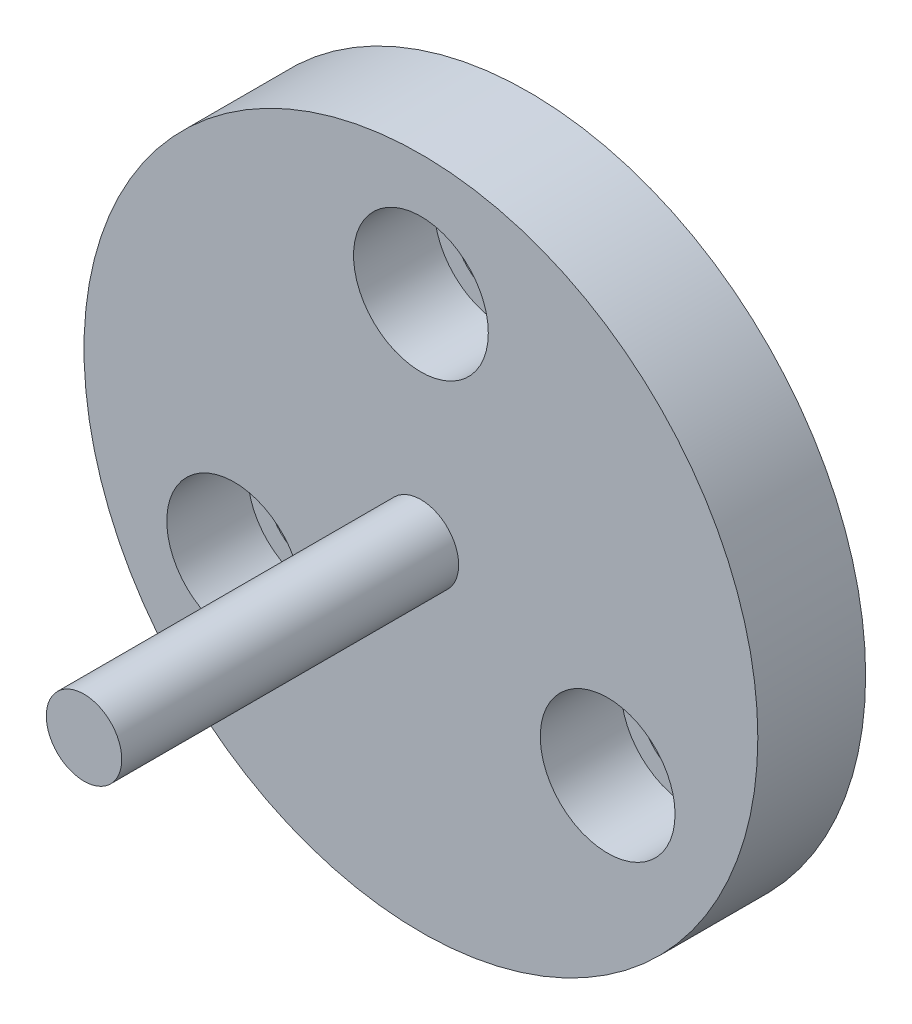
SolidWorks part; units mm, degrees
note: The reader was unsure of these and kept them because the rebuilt part matched: shared geometry of "草图1<3>", "草图3<3>".
ref_plane "前视基准面" through (0, 0, 0) normal (0, 0, 1) x (1, 0, 0)
ref_plane "上视基准面" through (0, 0, 0) normal (0, 1, 0) x (1, 0, 0)
ref_plane "右视基准面" through (0, 0, 0) normal (1, 0, 0) x (0, 0, -1)
other "Configuration Table"
sketch "草图1" plane through (0, 0, 0) normal (0, 0, 1) x (1, 0, 0)
  line L0 (0, 0) -> (1.6914, 0.6156) construction
  line L1 (0, 0) -> (1.5832, 0.5954)
  line L2 (0, 0) -> (1.5832, -0.5954)
  line L3 (0, 0) -> (1.6914, -0.6156) construction
  line L4 (0, 0) -> (2.55, 0) construction
  line L5 (1.6914, 0.6156) -> (1.6914, -0.6156) construction
  circle A0 centre (0, 0) radius 1.65
  circle A1 centre (0, 0) radius 2.55
  circle A2 centre (0, 0) radius 1.6914 construction
  circle A3 centre (0, 0) radius 1.8 construction
  circle A4 centre (0, 0) radius 3
  spline S0 degree 4 poles (1.5832, 0.5954) (1.5953, 0.5999) (1.6299, 0.61) (1.6985, 0.6188) (1.8107, 0.6176) (1.9542, 0.5935) (2.1323, 0.5368) (2.3288, 0.4397) (2.527, 0.3033) (2.7182, 0.1281) (2.8863, -0.0692) (3.0309, -0.2841) (3.1583, -0.5243) (3.284, -0.8365) (3.3855, -1.2255) (3.4358, -1.6902) (3.4119, -2.2085) (3.3126, -2.7182) (3.1474, -3.2089) (2.918, -3.6756) (2.6387, -4.1089) (2.3029, -4.5102) (1.9385, -4.866) (1.5141, -5.1906) (1.1742, -5.4065) (0.7714, -5.6132) (0.5343, -5.7151) (0.2601, -5.8236) (0.1183, -5.8645) (-0.005, -5.9055) (-0.0434, -5.9147) (-0.0704, -5.9226) (-0.0848, -5.927) knots 0 0 0 0 0 0.005604 0.015718 0.02996 0.048734 0.068727 0.096889 0.125051 0.153212 0.181374 0.209535 0.237696 0.271429 0.327752 0.384075 0.440398 0.496721 0.553044 0.609367 0.66569 0.722013 0.778336 0.834659 0.890982 0.909091 0.954545 0.977273 0.988636 0.994318 1 1 1 1 1 construction
  spline S1 degree 4 poles (1.5832, 0.5954) (1.5953, 0.5999) (1.6299, 0.61) (1.6985, 0.6188) (1.8107, 0.6176) (1.9542, 0.5935) (2.1323, 0.5368) (2.3288, 0.4397) (2.527, 0.3033) (2.7182, 0.1281) (2.8863, -0.0692) (3.0309, -0.2841) (3.1583, -0.5243) (3.284, -0.8365) (3.3855, -1.2255) (3.4358, -1.6902) (3.4119, -2.2085) (3.3126, -2.7182) (3.1474, -3.2089) (2.918, -3.6756) (2.6387, -4.1089) (2.3029, -4.5102) (1.9385, -4.866) (1.5141, -5.1906) (1.1742, -5.4065) (0.8753, -5.5599) (0.734, -5.626) (0.6996, -5.6416) knots 0 0 0 0 0 0.005604 0.015718 0.02996 0.048734 0.068727 0.096889 0.125051 0.153212 0.181374 0.209535 0.237696 0.271429 0.327752 0.384075 0.440398 0.496721 0.553044 0.609367 0.66569 0.722013 0.778336 0.834659 0.890982 0.909091 0.909091 0.909091 0.909091 0.909091
  spline S2 degree 4 poles (1.5832, -0.5954) (1.5953, -0.5999) (1.6299, -0.61) (1.6985, -0.6188) (1.8107, -0.6176) (1.9542, -0.5935) (2.1323, -0.5368) (2.3288, -0.4397) (2.527, -0.3033) (2.7182, -0.1281) (2.8863, 0.0692) (3.0309, 0.2841) (3.1583, 0.5243) (3.284, 0.8365) (3.3855, 1.2255) (3.4358, 1.6902) (3.4119, 2.2085) (3.3126, 2.7182) (3.1474, 3.2089) (2.918, 3.6756) (2.6387, 4.1089) (2.3029, 4.5102) (1.9385, 4.866) (1.5141, 5.1906) (1.1742, 5.4065) (0.7714, 5.6132) (0.5343, 5.7151) (0.2601, 5.8236) (0.1183, 5.8645) (-0.005, 5.9055) (-0.0434, 5.9147) (-0.0704, 5.9226) (-0.0848, 5.927) knots 0 0 0 0 0 0.005604 0.015718 0.02996 0.048734 0.068727 0.096889 0.125051 0.153212 0.181374 0.209535 0.237696 0.271429 0.327752 0.384075 0.440398 0.496721 0.553044 0.609367 0.66569 0.722013 0.778336 0.834659 0.890982 0.909091 0.954545 0.977273 0.988636 0.994318 1 1 1 1 1 construction
  spline S3 degree 4 poles (1.5832, -0.5954) (1.5953, -0.5999) (1.6299, -0.61) (1.6985, -0.6188) (1.8107, -0.6176) (1.9542, -0.5935) (2.1323, -0.5368) (2.3288, -0.4397) (2.527, -0.3033) (2.7182, -0.1281) (2.8863, 0.0692) (3.0309, 0.2841) (3.1583, 0.5243) (3.284, 0.8365) (3.3855, 1.2255) (3.4358, 1.6902) (3.4119, 2.2085) (3.3126, 2.7182) (3.1474, 3.2089) (2.918, 3.6756) (2.6387, 4.1089) (2.3029, 4.5102) (1.9385, 4.866) (1.5141, 5.1906) (1.1742, 5.4065) (0.8753, 5.5599) (0.734, 5.626) (0.6996, 5.6416) knots 0 0 0 0 0 0.005604 0.015718 0.02996 0.048734 0.068727 0.096889 0.125051 0.153212 0.181374 0.209535 0.237696 0.271429 0.327752 0.384075 0.440398 0.496721 0.553044 0.609367 0.66569 0.722013 0.778336 0.834659 0.890982 0.909091 0.909091 0.909091 0.909091 0.909091
  point P16 (1.6914, 0)
  dimension "内啮合齿顶圆直径" = 3.3
  dimension "内啮合分度圆直径" = 3.6
  dimension "内啮合基圆直径" = 3.3829
  dimension "内啮合齿根圆直径" = 5.1
  dimension "外径" = 6
  dimension "渐开线镜像线夹角" = 20
extrude "凸台-拉伸1" add sketch "草图1" along normal blind 4 contours A4 | A0
extrude "切除-拉伸2" cut sketch "草图1<3>" along normal through all contours A0 S3 A1 S1
sketch "草图1<3>" plane through (0, 0, 0) normal (0, 0, 1) x (1, 0, 0) same geometry as "草图1"
pattern_circular "阵列(圆周)1" count 9 over 360 about axis through (0, 0, 4) along (0, 0, 1) of "切除-拉伸2"
sketch "草图2" plane through (0, 0, 0) normal (0, 0, -1) x (-1, 0, 0)
  circle A0 centre (0, 0) radius 3
  circle A1 centre (0, 0) radius 3 construction
  circle A2 centre (0, 0) radius 5
  dimension "D1" = 10
extrude "凸台-拉伸2" add sketch "草图2" against normal up to surface (4 mm away) contours A2 up to face at (3, 0, 4)
sketch "草图3" plane through (0, 0, 0) normal (0, 0, 1) x (1, 0, 0)
  circle A0 centre (0, 8) radius 2.5
  circle A1 centre (0, 8) radius 1.8
  circle A2 centre (0, 0) radius 12.5
  circle A3 centre (6.9282, -4) radius 1.8
  circle A4 centre (6.9282, -4) radius 2.5
  circle A5 centre (-6.9282, -4) radius 1.8
  circle A6 centre (-6.9282, -4) radius 2.5
  circle A7 centre (0, 0) radius 5
  circle A10 centre (0, 0) radius 5 construction
  point P14 (0, 0)
  dimension "D4" = 3.6
  dimension "D5" = 5
  dimension "D1" = 25
  dimension "D2" = 3
  dimension "D3" = 8
extrude "凸台-拉伸4" add sketch "草图3" along normal blind 4 contours A2 | A5 | A3 | A1 | A7
extrude "切除-拉伸3" cut sketch "草图3<3>" against normal offset from surface (3 mm away) 1 from surface at 4 contours A0 | A4 | A6 up to face at (12.5, 0, 0) starting at face at (1.8, 8, 4)
sketch "草图3<3>" plane through (0, 0, 0) normal (0, 0, 1) x (1, 0, 0) same geometry as "草图3"
sketch "草图4" plane through (0, 0, 4) normal (0, 0, 1) x (1, 0, 0)
  circle A0 centre (0, 0) radius 1.4
  dimension "D1" = 2.8
extrude "凸台-拉伸5" add sketch "草图4" along normal blind 12.5 from surface at 0 starting at face at (2.5, 8, 4)
equation "\"m\"= 0.4'模数"
equation "\"z1\"= 9'外啮合齿轮数"
equation "\"a\"= 20度'压力角"
equation "\"z2\"= 9'内啮合齿轮数"
equation "\"hax\"= 1'齿顶高系数"
equation "\"cx\"= 0.25'顶隙系数"
equation "\"ha\"= \"hax\" * \"m\"'齿顶高"
equation "\"hf\"= ( \"hax\" + \"cx\" ) * \"m\"'齿根高"
equation "\"d1\"= \"m\" * \"z1\"'外啮合分度圆直径"
equation "\"da1\"= ( \"z1\" + 2 ) * \"m\"'外啮合齿顶圆直径"
equation "\"df1\"= \"d1\" - 2 * \"hf\"'外啮合齿根圆直径"
equation "\"db1\"= \"d1\" * cos ( \"a\" )'外啮合基圆直径"
equation "\"p\"= \"m\" * PI'齿距"
equation "\"d2\"= \"m\" * \"z2\"'内啮合分度圆直径"
equation "\"db2\"= \"d2\" * cos ( \"a\" )'内啮合基圆直径"
equation "\"da2\"= ( \"z2\" - 2 ) * \"m\"'内啮合齿顶圆直径"
equation "\"df2\"= \"d2\" + 2 * \"hf\"'内啮合齿根圆直径"
equation "\"内啮合齿顶圆直径@草图1\" = \"da2\" + 1 * \"hf\""
equation "\"内啮合齿根圆直径@草图1\" = \"df2\" + 1 * \"hf\""
equation "\"内啮合分度圆直径@草图1\"= \"d2\""
equation "\"内啮合基圆直径@草图1\"= \"db2\""
equation "\"渐开线镜像线夹角@草图1\"= 360度 / 4 / \"z2\" + 360度 / 4 / \"z2\""
equation "\"do\"= IIF ( \"edo\" >= ( \"df2\" + 1 ) , \"edo\" , ( \"df2\" + 1 ) )'外圈直径"
equation "\"h\"= 4'厚度"
equation "\"外径@草图1\"= \"do\""
equation "\"厚度@凸台-拉伸1\"= \"h\""
equation "\"内啮合齿轮数@阵列(圆周)1\"= \"z2\""
equation "\"edo\"= 6'期望的外圈直径"
